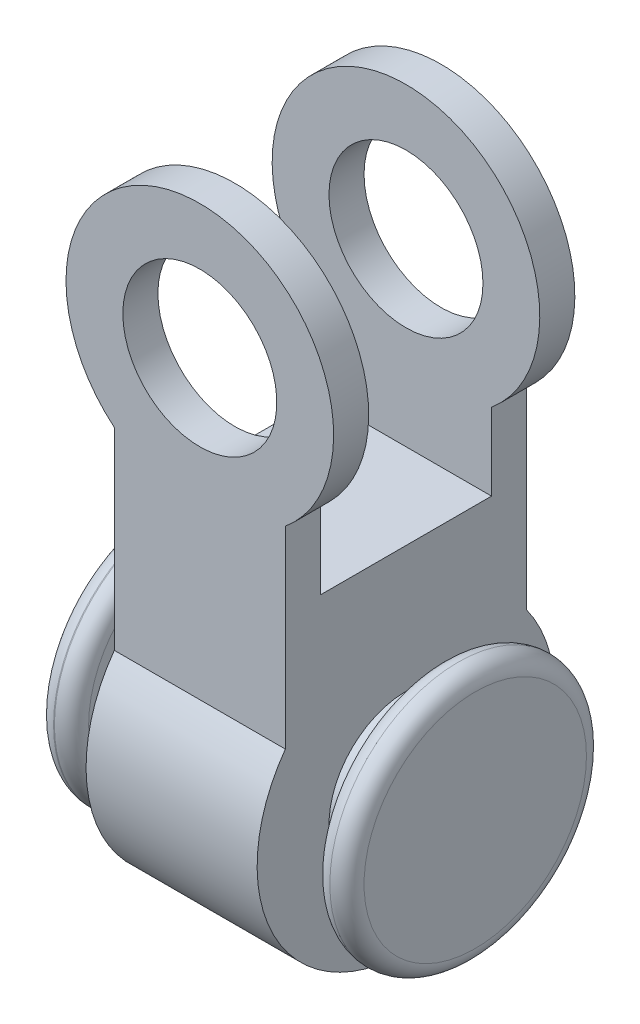
SolidWorks part; units mm, degrees
ref_plane "Front Plane" through (0, 0, 0) normal (0, 0, 1) x (1, 0, 0)
ref_plane "Top Plane" through (0, 0, 0) normal (0, 1, 0) x (1, 0, 0)
ref_plane "Right Plane" through (0, 0, 0) normal (1, 0, 0) x (0, 0, -1)
sketch "Sketch1" plane through (0, 0, 0) normal (1, 0, 0) x (0, 0, -1)
  circle A0 centre (0, 0) radius 87
  dimension "D1" = 174
extrude "Boss-Extrude3" add sketch "Sketch1" along normal blind 100
sketch "Sketch2" plane through (100, 0, 0) normal (1, 0, 0) x (0, 0, -1)
  circle A0 centre (0, 0) radius 45
  dimension "D1" = 90
extrude "Boss-Extrude4" add sketch "Sketch2" along normal blind 20.5
sketch "Sketch3" plane through (120.5, 0, 0) normal (1, 0, 0) x (0, 0, -1)
  circle A0 centre (0, 0) radius 75
  dimension "D1" = 150
extrude "Boss-Extrude5" add sketch "Sketch3" along normal blind 20
fillet "Fillet1" radius 10 2 edges at (120.5, 0, -75) (140.5, 0, -75)
sketch "Sketch4" plane through (0, 0, 0) normal (-1, 0, 0) x (0, 0, 1)
  circle A0 centre (0, 0) radius 45
  dimension "D1" = 90
extrude "Boss-Extrude6" add sketch "Sketch4" along normal blind 20.5
sketch "Sketch5" plane through (-20.5, 0, 0) normal (-1, 0, 0) x (0, 0, 1)
  circle A0 centre (0, 0) radius 75
  dimension "D1" = 150
extrude "Boss-Extrude7" add sketch "Sketch5" along normal blind 20.5
fillet "Fillet2" radius 10 2 edges at (-20.5, 0, 75) (-41, 0, 75)
ref_plane "Plane1" through (0, 87, 0) normal (0, 1, 0) x (1, 0, 0)
sketch "Sketch6" plane through (0, 87, 0) normal (0, 1, 0) x (1, 0, 0)
  line L0 (0, 87) -> (0, -87) construction
  line L1 (100, 70.5) -> (0, 70.5)
  line L2 (100, 70.5) -> (100, -70.5)
  line L3 (100, -70.5) -> (0, -70.5)
  line L4 (0, 70.5) -> (0, -70.5)
  line L5 (100, 70.5) -> (0, -70.5) construction
  line L6 (100, -70.5) -> (0, 70.5) construction
  point P0 (50, 0)
  point P5 (100, 0)
  dimension "D1" = 70.5
  dimension "D2" = 100
  dimension "D3" = 50
extrude "Boss-Extrude8" add sketch "Sketch6" against normal up to next
ref_plane "Plane4" through (0, 0, -70.5) normal (0, 0, -1) x (-1, 0, 0)
sketch "Sketch9" plane through (0, 0, -70.5) normal (0, 0, -1) x (-1, 0, 0)
  line L0 (-100, 87) -> (0, 87) construction
  line L2 (-100, 87) -> (0, 87)
  line L3 (-100, 87) -> (-100, 163.8467)
  line L5 (0, 87) -> (0, 163.8467)
  arc A0 (0, 163.8467) -> (-100, 163.8467) centre (-50, 224) ccw
  circle A1 centre (-50, 224) radius 45
  dimension "D4" = 90
  dimension "D1" = 137
  dimension "D2" = 100
  dimension "D3" = 76.8467
extrude "Boss-Extrude10" add sketch "Sketch9" against normal blind 141
ref_plane "Plane7" through (100, 0, 0) normal (-1, 0, 0) x (0, 1, 0)
ref_plane "Plane8" through (147, 0, 0) normal (-1, 0, 0) x (0, 1, 0)
sketch "Sketch21" plane through (147, 0, 0) normal (-1, 0, 0) x (0, 1, 0)
  line L0 (163.8467, -70.5) -> (302.2204, -70.5) construction
  line L5 (87.9847, 70.5) -> (-87.9847, 70.5) construction
  line L6 (335.5696, 50) -> (118.8, 50)
  line L7 (335.5696, 50) -> (335.5696, -50)
  line L8 (335.5696, -50) -> (118.8, -50)
  line L9 (118.8, 50) -> (118.8, -50)
  line L10 (335.5696, 50) -> (118.8, -50) construction
  line L11 (335.5696, -50) -> (118.8, 50) construction
  point P0 (227.1848, 0)
  dimension "D1" = 70.5
  dimension "D2" = 118.8
  dimension "D3" = 20.5
extrude "Cut-Extrude2" cut sketch "Sketch21" along normal through all both and the other way through all
ref_plane "Plane9" through (50, 0, 0) normal (1, 0, 0) x (0, 0, -1)
sketch "Sketch22" plane through (0, 0, -70.5) normal (0, 0, -1) x (-1, 0, 0)
  point P0 (-50, 224)
sketch "Sketch23" plane through (0, 0, 70.5) normal (0, 0, 1) x (1, 0, 0)
  point P0 (50, 224)
